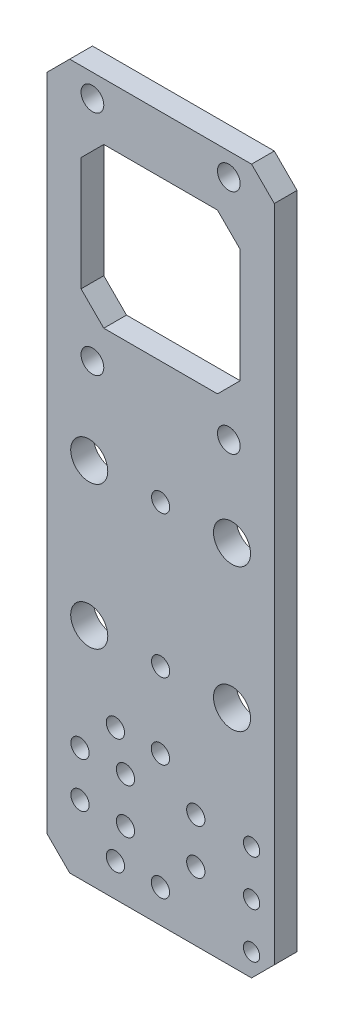
SolidWorks part; units mm, degrees
material "5052-O"
ref_plane "Front Plane" through (0, 0, 0) normal (0, 0, 1) x (1, 0, 0)
ref_plane "Top Plane" through (0, 0, 0) normal (0, 1, 0) x (1, 0, 0)
ref_plane "Right Plane" through (0, 0, 0) normal (1, 0, 0) x (0, 0, -1)
sketch "Sketch1" plane through (0, 0, 0) normal (0, 0, 1) x (1, 0, 0)
  line L1 (-31.75, -82.55) -> (31.75, -82.55)
  line L2 (-31.75, -82.55) -> (-31.75, 114.3)
  line L3 (-31.75, 114.3) -> (31.75, 114.3)
  line L4 (31.75, -82.55) -> (31.75, 114.3)
  line L5 (-31.75, -82.55) -> (31.75, 114.3) construction
  line L6 (-31.75, 114.3) -> (31.75, -82.55) construction
  point P0 (0, 0)
  point P7 (0, 114.3)
  dimension "D1" = 82.55
  dimension "D2" = 63.5
  dimension "D3" = 114.3
extrude "Boss-Extrude1" add sketch "Sketch1" along normal mid plane 6.35
sketch "Sketch2" plane through (0, 0, 3.175) normal (0, 0, 1) x (1, 0, 0)
  line L0 (31.75, 114.3) -> (-31.75, 114.3) construction
  line L1 (-19.939, 19.939) -> (19.939, 19.939) construction
  line L2 (-19.939, 19.939) -> (-19.939, -19.939) construction
  line L3 (-19.939, -19.939) -> (19.939, -19.939) construction
  line L4 (19.939, 19.939) -> (19.939, -19.939) construction
  line L5 (-19.939, 19.939) -> (19.939, -19.939) construction
  line L6 (-19.939, -19.939) -> (19.939, 19.939) construction
  line L9 (0, -19.85) -> (0, 19.85) construction
  circle A8 centre (-19.939, -19.939) radius 2 construction
  circle A9 centre (19.939, -19.939) radius 2 construction
  circle A10 centre (19.939, 19.939) radius 2 construction
  circle A11 centre (-19.939, 19.939) radius 2 construction
  arc A13 (2.5159, 20.1991) -> (2.5158, 20.2) centre (0, 19.85) ccw
  circle A14 centre (0, -19.85) radius 2.54
  circle A17 centre (0, 19.85) radius 2.54
  circle A18 centre (-19.939, 19.939) radius 5.175
  circle A19 centre (19.939, 19.939) radius 5.175
  circle A20 centre (19.939, -19.939) radius 5.175
  circle A21 centre (-19.939, -19.939) radius 5.175
  point P3 (0, 0)
  point P7 (0, 0)
  point P15 (0, 0)
  point P35 (0, 114.3)
  dimension "D5" = 10.35
  dimension "D4" = 5.08
  dimension "D2" = 39.878
  dimension "D3" = 39.7
  dimension "D1" = 3.175
extrude "Cut-Extrude1" cut sketch "Sketch2" against normal through all contours A11 | A10 | A13 A17 | A9 | A14 | A8 | A18 | A21 | A20 | A19 region at (0, 19.85, 3.175) region at (0, -19.85, 3.175) region at (-19.939, 19.939, 3.175) region at (19.939, 19.939, 3.175) region at (19.939, -19.939, 3.175) region at (-19.939, -19.939, 3.175)
sketch "Sketch3" plane through (0, 0, 3.175) normal (0, 0, 1) x (1, 0, 0)
  line L0 (31.75, 114.3) -> (-31.75, 114.3) construction
  line L1 (-22.225, 53.975) -> (22.225, 53.975)
  line L2 (-22.225, 53.975) -> (-22.225, 98.425)
  line L3 (-22.225, 98.425) -> (22.225, 98.425)
  line L4 (22.225, 53.975) -> (22.225, 98.425)
  line L5 (-22.225, 53.975) -> (22.225, 98.425) construction
  line L6 (-22.225, 98.425) -> (22.225, 53.975) construction
  point P0 (0, 76.2)
  point P9 (0, 114.3)
  dimension "D1" = 44.45
  dimension "D2" = 38.1
extrude "Cut-Extrude2" cut sketch "Sketch3" against normal through all
sketch "Sketch4" plane through (0, 0, 3.175) normal (0, 0, 1) x (1, 0, 0)
  line L0 (22.225, 98.425) -> (-22.225, 98.425) construction
  line L1 (-19.05, 44.45) -> (19.05, 44.45) construction
  line L2 (-19.05, 44.45) -> (-19.05, 107.95) construction
  line L3 (-19.05, 107.95) -> (19.05, 107.95) construction
  line L4 (19.05, 44.45) -> (19.05, 107.95) construction
  line L5 (-19.05, 44.45) -> (19.05, 107.95) construction
  line L6 (-19.05, 107.95) -> (19.05, 44.45) construction
  line L7 (-22.225, 98.425) -> (-22.225, 53.975) construction
  circle A0 centre (-19.05, 107.95) radius 3.175
  circle A1 centre (19.05, 107.95) radius 3.175
  circle A2 centre (19.05, 44.45) radius 3.175
  circle A3 centre (-19.05, 44.45) radius 3.175
  point P8 (0, 76.2)
  point P15 (0, 98.425)
  point P18 (-22.225, 76.2)
  dimension "D3" = 6.35
  dimension "D1" = 38.1
  dimension "D2" = 63.5
extrude "Cut-Extrude3" cut sketch "Sketch4" against normal through all
chamfer "Chamfer1" distance 6.35 angle 45 8 edges at (31.75, -82.55, 0) (-31.75, -82.55, 0) (31.75, 114.3, 0) (-31.75, 114.3, 0) (-22.225, 53.975, 0) (22.225, 53.975, 0) (22.225, 98.425, 0) (-22.225, 98.425, 0)
sketch "Sketch5" plane through (0, 0, -3.175) normal (0, 0, -1) x (-1, 0, 0)
  line L0 (-25.4, -50.8) -> (-25.4, -63.5) construction
  line L1 (-25.4, -63.5) -> (-25.4, -76.2) construction
  line L2 (25.4, -82.55) -> (-25.4, -82.55) construction
  line L3 (-31.75, -76.2) -> (-31.75, 107.95) construction
  circle A0 centre (-25.4, -50.8) radius 2.286
  circle A1 centre (-25.4, -63.5) radius 2.286
  circle A2 centre (-25.4, -76.2) radius 2.286
  dimension "D1" = 4.572
  dimension "D2" = 6.35
  dimension "D3" = 12.7
  dimension "D4" = 6.35
extrude "Cut-Extrude4" cut sketch "Sketch5" against normal through all
sketch "Sketch6" plane through (0, 0, 3.175) normal (0, 0, 1) x (1, 0, 0)
  line L0 (-22.5145, -50.8638) -> (-12.6362, -40.9855) construction
  line L1 (-22.5145, -50.8638) -> (-0.0638, -73.3145) construction
  line L2 (-12.6362, -40.9855) -> (9.8145, -63.4362) construction
  line L3 (-0.0638, -73.3145) -> (9.8145, -63.4362) construction
  line L4 (-12.6362, -40.9855) -> (-0.0638, -73.3145) construction
  line L5 (-25.4, -82.55) -> (25.4, -82.55) construction
  line L7 (-31.75, 107.95) -> (-31.75, -76.2) construction
  point P2 (-6.35, -57.15)
  point P3 (9.8145, -63.4362)
  point P5 (-12.6362, -40.9855)
  point P6 (-22.5145, -50.8638)
  point P7 (-0.0638, -73.3145)
  point P13 (4.8753, -68.3753)
  point P14 (-17.5753, -45.9247)
  point P15 (-11.2891, -62.0891)
  point P16 (-1.4109, -52.2109)
  dimension "D1" = 25.4
  dimension "D2" = 31.75
  dimension "D3" = 13.97
  dimension "D4" = 25.4
  dimension "D5" = 45
hole_wizard "#10 Clearance Hole1" positions "Sketch7" profile "Sketch8" hole size "#10" standard "ANSI Inch"
sketch "Sketch7" plane through (0, 0, 3.175) normal (0, 0, 1) x (1, 0, 0)
  point P0 (-22.5145, -50.8638)
  point P3 (-12.6362, -40.9855)
  point P6 (9.8145, -63.4362)
  point P9 (-0.0638, -73.3145)
sketch "Sketch8" plane through (-22.5145, -50.8638, 3.175) normal (1, 0, 0) x (0, -1, 0)
  line L0 (0, 0) -> (0, 20.5838)
  line L1 (0, 20.5838) -> (2.5527, 19.05)
  line L2 (2.5527, 19.05) -> (2.5527, 0)
  line L5 (2.5527, 0) -> (0, 0)
  line L10 (0, 20.5838) -> (-2.5527, 19.05) construction
  line L11 (0, -6.35) -> (0, 107.95) construction
  dimension "Hole Dia." = 5.1054
  dimension "Hole Depth" = 19.05
  dimension "Drill Angle" = 118
ref_plane "Plane1" through (-6.35, 0, 0) normal (-1, 0, 0) x (0, 0, 1)
mirror "Mirror1" about plane through (-6.35, 0, 0) normal (-1, 0, 0) of "#10 Clearance Hole1"
sketch "Sketch9" plane through (0, 0, 3.175) normal (0, 0, 1) x (1, 0, 0)
  circle A0 centre (-9.8145, -50.8638) radius 2.5527
  circle A1 centre (-9.8145, -63.4362) radius 2.5527
  circle A2 centre (-22.5145, -50.8638) radius 2.5527 construction
  point P4 (-22.5145, -63.4362)
  dimension "D1" = 12.7
extrude "Cut-Extrude6" cut sketch "Sketch9" against normal through all
